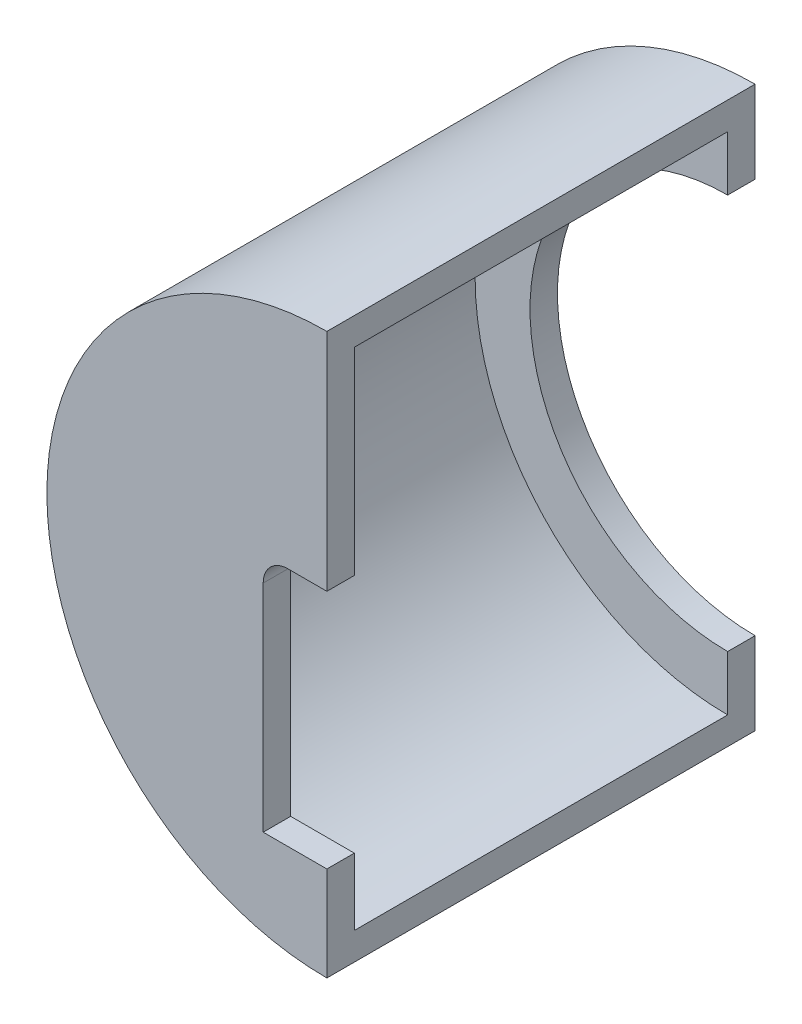
SolidWorks part; units mm, degrees
ref_plane "Plan de face" through (0, 0, 0) normal (0, 0, 1) x (1, 0, 0)
ref_plane "Plan de dessus" through (0, 0, 0) normal (0, 1, 0) x (1, 0, 0)
ref_plane "Plan de droite" through (0, 0, 0) normal (1, 0, 0) x (0, 0, -1)
sketch "Esquisse1" plane through (0, 0, 0) normal (0, 0, 1) x (1, 0, 0)
  line L0 (0, 54.1543) -> (0, -54.1543) construction
  line L1 (-103.4367, 0) -> (52.1834, 0) construction
  line L2 (0, 51) -> (0, 46)
  line L3 (0, -46) -> (0, -51)
  arc A0 (0, 46) -> (0, -46) centre (0, 0) ccw
  arc A1 (0, 51) -> (0, -51) centre (0, 0) ccw
  dimension "D1" = 46
  dimension "D2" = 5
extrude "Boss.-Extru.1" add sketch "Esquisse1" along normal mid plane 68
sketch "Esquisse2" plane through (0, 0, 34) normal (0, 0, 1) x (1, 0, 0)
  line L0 (0, 51) -> (0, -51)
  arc A0 (0, 51) -> (0, -51) centre (0, 0) ccw
  arc A1 (0, 51) -> (0, -51) centre (0, 0) ccw construction
extrude "Boss.-Extru.2" add sketch "Esquisse2" along normal blind 5
sketch "Esquisse3" plane through (0, 0, -34) normal (0, 0, -1) x (-1, 0, 0)
  line L0 (0, 51) -> (0, 36)
  line L1 (0, -51) -> (0, -36)
  arc A0 (0, -51) -> (0, 51) centre (0, 0) ccw
  arc A1 (0, -51) -> (0, 51) centre (0, 0) ccw construction
  arc A2 (0, -36) -> (0, 36) centre (0, 0) ccw
  arc A3 (0, -46) -> (0, 46) centre (0, 0) ccw construction
  dimension "D1" = 10
extrude "Boss.-Extru.3" add sketch "Esquisse3" along normal blind 5
sketch "Esquisse4" plane through (0, 0, 39) normal (0, 0, 1) x (1, 0, 0)
  line L1 (-11.6, -2) -> (11.6, -2)
  line L2 (-11.6, -2) -> (-11.6, -33.8)
  line L3 (-11.6, -33.8) -> (11.6, -33.8)
  line L4 (11.6, -2) -> (11.6, -33.8)
  line L5 (-11.6, -2) -> (-11.6, 5.5)
  line L6 (11.6, -2) -> (11.6, 5.5)
  line L7 (-7.1, 10) -> (7.1, 10)
  arc A0 (-11.6, 5.5) -> (-7.1, 10) centre (-7.1, 5.5) cw
  arc A1 (7.1, 10) -> (11.6, 5.5) centre (7.1, 5.5) cw
  circle A2 centre (0, 0) radius 2.15
  line M20 (0, -51) -> (0, 51)
  dimension "D3" = 4.3
  dimension "D6" = 4.5
  dimension "D7" = 4.5
  dimension "D1" = 2
  dimension "D2" = 11.6
  dimension "D4" = 43.8
  dimension "D5" = 23.2
  dimension "D8" = 12
extrude "Enlèv. mat.-Extru.1" cut sketch "Esquisse4" against normal blind 10 contours A2 L7 A0 L5 L1 M20 | A2 L1 M20 | A2 L1 L2 L3 M20 | A2 region at (-5.9113, 4.0537, 39) region at (-5.8012, -17.9034, 39) region at (-0.9193, 0.0228, 39)
